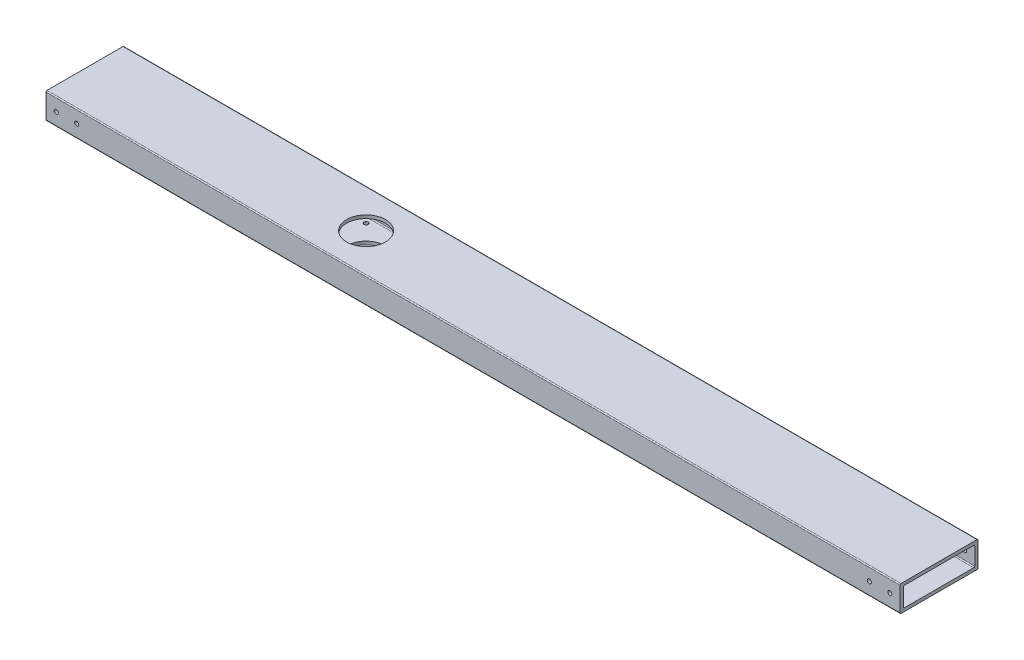
SolidWorks part; units mm, degrees
ref_plane "Front Plane" through (0, 0, 0) normal (0, 0, 1) x (1, 0, 0)
ref_plane "Top Plane" through (0, 0, 0) normal (0, 1, 0) x (1, 0, 0)
ref_plane "Right Plane" through (0, 0, 0) normal (1, 0, 0) x (0, 0, -1)
sketch "Sketch1" plane through (0, 0, 0) normal (1, 0, 0) x (0, 0, -1)
  line L1 (38.1, -12.7) -> (-38.1, -12.7)
  line L2 (38.1, -12.7) -> (38.1, 12.7)
  line L3 (38.1, 12.7) -> (-38.1, 12.7)
  line L4 (-38.1, -12.7) -> (-38.1, 12.7)
  line L5 (38.1, -12.7) -> (-38.1, 12.7) construction
  line L6 (38.1, 12.7) -> (-38.1, -12.7) construction
  line L7 (34.925, -9.525) -> (-34.925, -9.525)
  line L8 (34.925, -9.525) -> (34.925, 9.525)
  line L9 (34.925, 9.525) -> (-34.925, 9.525)
  line L10 (-34.925, -9.525) -> (-34.925, 9.525)
  line L11 (34.925, -9.525) -> (-34.925, 9.525) construction
  line L12 (34.925, 9.525) -> (-34.925, -9.525) construction
  point P0 (0, 0)
  point P6 (0, 0)
  dimension "D1" = 76.2
  dimension "D2" = 25.4
  dimension "D3" = 3.175
  dimension "D4" = 3.175
extrude "Boss-Extrude1" add sketch "Sketch1" along normal mid plane 835
fillet "Fillet1" radius 1 8 edges at (0, -12.7, -38.1) (0, 9.525, -34.925) (0, -9.525, 34.925) (0, 9.525, 34.925) (0, -12.7, 38.1) (0, -9.525, -34.925) (0, 12.7, -38.1) (0, 12.7, 38.1)
sketch "Sketch2" plane through (0, 12.7, 0) normal (0, 1, 0) x (1, 0, 0)
  line L0 (-417.5, 37.1) -> (-417.5, -37.1) construction
  circle A0 centre (-142.7, 0) radius 19
  dimension "D1" = 38
  dimension "D2" = 274.8
extrude "Cut-Extrude1" cut sketch "Sketch2" against normal through all
sketch "Sketch3" plane through (0, 12.7, 0) normal (0, 1, 0) x (1, 0, 0)
  line L1 (-197.2494, -25.5518) -> (-243.937, -25.5518)
  line L2 (-197.2494, -25.5518) -> (-197.2494, 25.5518)
  line L3 (-197.2494, 25.5518) -> (-243.937, 25.5518)
  line L4 (-243.937, -25.5518) -> (-243.937, 25.5518)
  line L5 (-197.2494, -25.5518) -> (-243.937, 25.5518) construction
  line L6 (-197.2494, 25.5518) -> (-243.937, -25.5518) construction
  point P0 (-220.5932, 0)
split line "Split Line1" [suppressed]
sketch "Sketch4" plane through (0, 0, 38.1) normal (0, 0, 1) x (1, 0, 0)
  line L0 (-417.5, 11.7) -> (-417.5, -11.7) construction
  point P0 (-407.5, 0)
  point P2 (-387.5, 0)
  dimension "D1" = 20
  dimension "D2" = 10
hole_wizard "Ø4.0mm Dowel Hole1" positions "Sketch4" profile "Sketch5" hole size "Ø4.0" standard "ANSI Metric" end condition through all
sketch "Sketch5" plane through (-407.5, 0, 38.1) normal (1, 0, 0) x (0, -1, 0)
  line L0 (0, 0) -> (0, 76.2)
  line L1 (0, 76.2) -> (2, 76.2)
  line L2 (2, 76.2) -> (2, 0)
  line L5 (2, 0) -> (0, 0)
  line L11 (0, -6.35) -> (0, 107.95) construction
  dimension "Thru Hole Dia." = 4
  dimension "Thru Hole Depth" = 76.2
mirror "Mirror1" about plane through (0, 0, 0) normal (1, 0, 0) of "Ø4.0mm Dowel Hole1"
hole_wizard "Ø4.0mm Dowel Hole2" positions "Sketch6" profile "Sketch7" hole size "Ø4.0" standard "ANSI Metric" end condition up to next
sketch "Sketch6" plane through (0, -12.7, 0) normal (0, -1, 0) x (-1, 0, 0)
  line L0 (114.1329, -28.5671) -> (171.2671, -28.5671) construction
  line L1 (171.2671, -28.5671) -> (171.2671, 28.5671) construction
  line L2 (171.2671, 28.5671) -> (114.1329, 28.5671) construction
  line L3 (114.1329, 28.5671) -> (114.1329, -28.5671) construction
  circle A1 centre (142.7, 0) radius 25.4 construction
  circle A2 centre (142.7, 0) radius 40.4 construction
  point P1 (171.2671, -28.5671)
  point P3 (171.2671, 28.5671)
  point P5 (114.1329, 28.5671)
  point P7 (114.1329, -28.5671)
  point P21 (114.1329, 0)
  point P203 (142.7, 28.5671)
  dimension "D1" = 50.8
  dimension "D2" = 15
sketch "Sketch7" plane through (-171.2671, -12.7, 28.5671) normal (1, 0, 0) x (0, 0, -1)
  line L0 (0, 0) -> (0, 3.175)
  line L1 (0, 3.175) -> (2, 3.175)
  line L2 (2, 3.175) -> (2, 0)
  line L5 (2, 0) -> (0, 0)
  line L11 (0, -6.35) -> (0, 107.95) construction
  dimension "Thru Hole Dia." = 4
  dimension "Thru Hole Depth" = 3.175
